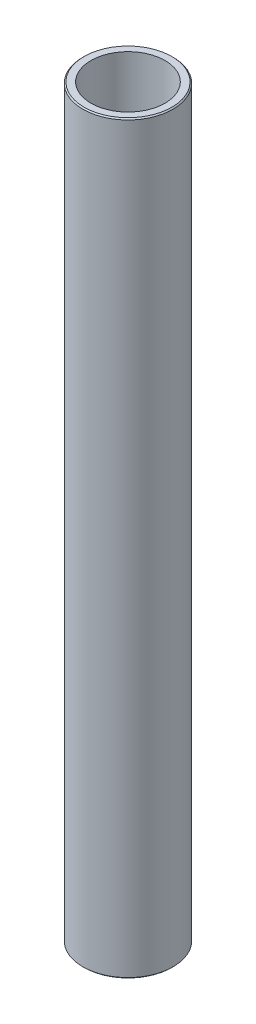
SolidWorks part; units mm, degrees
ref_plane "Front Plane" through (0, 0, 0) normal (0, 0, 1) x (1, 0, 0)
ref_plane "Top Plane" through (0, 0, 0) normal (0, 1, 0) x (1, 0, 0)
ref_plane "Right Plane" through (0, 0, 0) normal (1, 0, 0) x (0, 0, -1)
sketch "Sketch1" plane through (0, 0, 0) normal (0, 1, 0) x (1, 0, 0)
  circle A0 centre (0, 0) radius 35
  dimension "SHAFT_OD" = 70
extrude "Boss-Extrude1" add sketch "Sketch1" along normal blind 578.3308
sketch "Sketch2" plane through (0, 0, 0) normal (0, 1, 0) x (1, 0, 0)
  circle A0 centre (0, 0) radius 28.7453
  dimension "BORE_D" = 57.4906
extrude "Cut-Extrude1" cut sketch "Sketch2" along normal through all
chamfer "Chamfer1" distance 0.9163 angle 45 2 edges at (0, 578.3308, 35) (0, 0, 35)
